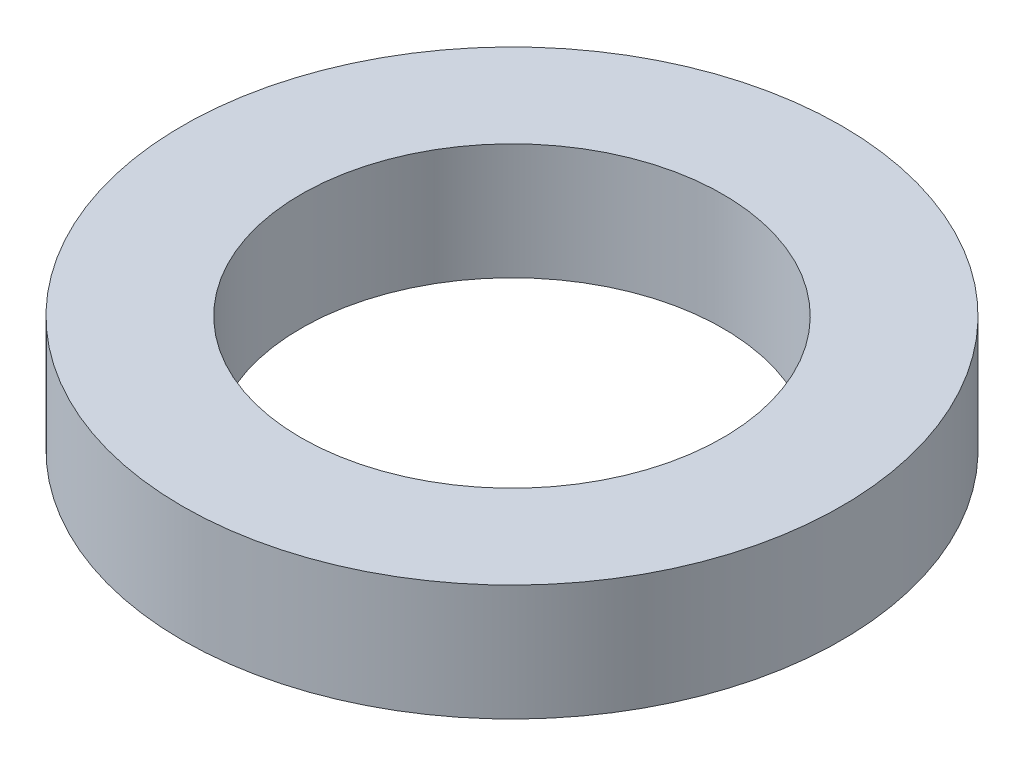
SolidWorks part; units mm, degrees
ref_plane "Front Plane" through (0, 0, 0) normal (0, 0, 1) x (1, 0, 0)
ref_plane "Top Plane" through (0, 0, 0) normal (0, 1, 0) x (1, 0, 0)
ref_plane "Right Plane" through (0, 0, 0) normal (1, 0, 0) x (0, 0, -1)
sketch "Sketch1" plane through (0, 0, 0) normal (0, 1, 0) x (1, 0, 0)
  circle A0 centre (0, 0) radius 62.5
  dimension "FLANGE_OD" = 125
extrude "Boss-Extrude1" add sketch "Sketch1" along normal blind 22
sketch "Sketch2" plane through (0, 0, 0) normal (0, 1, 0) x (1, 0, 0)
  circle A0 centre (0, 0) radius 40
  dimension "BORE_D" = 80
extrude "Cut-Extrude1" cut sketch "Sketch2" along normal through all
sketch "Sketch3" plane through (0, 22, 0) normal (0, 1, 0) x (1, 0, 0)
  circle A0 centre (0, 0) radius 21.5446 construction
  circle A1 centre (-21.5446, 0) radius 1.5415
  dimension "BOLT_D" = 3.0829
  dimension "BOLT_PCD" = 43.0891
extrude "Cut-Extrude2" cut sketch "Sketch3" against normal blind 16.2755 rebuild error yes
pattern_circular "CirPattern1" count 4 over 360 rebuild error yes
